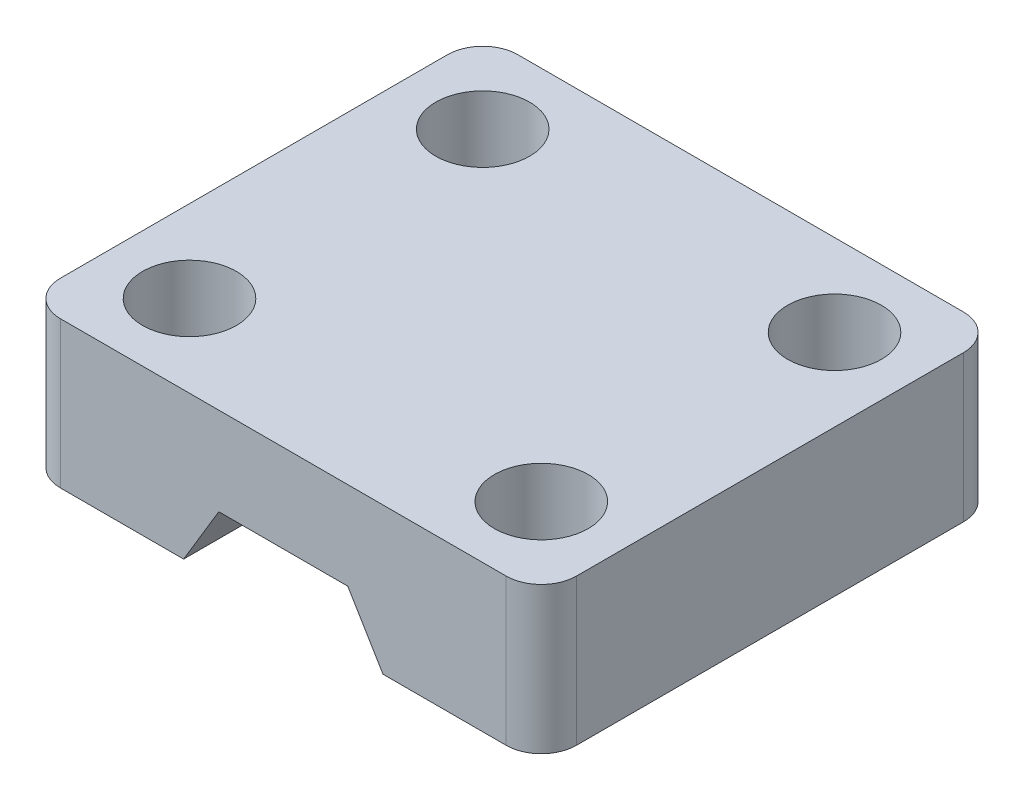
SolidWorks part; units mm, degrees
ref_plane "Front Plane" through (0, 0, 0) normal (0, 0, 1) x (1, 0, 0)
ref_plane "Top Plane" through (0, 0, 0) normal (0, 1, 0) x (1, 0, 0)
ref_plane "Right Plane" through (0, 0, 0) normal (1, 0, 0) x (0, 0, -1)
sketch "Sketch1" plane through (0, 0, 0) normal (0, 0, 1) x (1, 0, 0)
  line L0 (13.5, -12.5) -> (16.5, -7.5)
  line L1 (0, 0) -> (44, 0)
  line L2 (0, 0) -> (0, -12.5)
  line L3 (0, -12.5) -> (13.5, -12.5)
  line L4 (44, 0) -> (44, -12.5)
  line L5 (16.5, -7.5) -> (27.5, -7.5)
  line L6 (27.5, -7.5) -> (30.5, -12.5)
  line L7 (30.5, -12.5) -> (44, -12.5)
  point P9 (22, -7.5)
  point P10 (28.5675, -7.5)
  point P11 (22, 0)
  dimension "D1" = 17
  dimension "D2" = 11
  dimension "D3" = 5
  dimension "D4" = 8.5
  dimension "D5" = 12.5
  dimension "D6" = 44
extrude "Boss-Extrude1" add sketch "Sketch1" along normal blind 39
sketch "Sketch2" plane through (0, 0, 0) normal (0, 1, 0) x (1, 0, 0)
  line L0 (44, 0) -> (0, 0) construction
  line L2 (44, -39) -> (44, 0) construction
  circle A0 centre (7, -7) radius 4
  circle A1 centre (37, -7) radius 4
  circle A2 centre (37, -32) radius 4
  circle A3 centre (7, -32) radius 4
  point P8 (0, 0)
  point P9 (0, 0)
  point P10 (0, 0)
  point P11 (0, 0)
  point P12 (0, 0)
  point P15 (22, 0)
  point P18 (21.0709, -19.6822)
  point P21 (44, -19.5)
  dimension "D3" = 8
  dimension "D1" = 30
  dimension "D2" = 25
  dimension "D4" = 15
  dimension "D5" = 12.5
extrude "Cut-Extrude1" cut sketch "Sketch2" against normal through all
fillet "Fillet1" radius 3 4 edges at (0, -6.25, 0) (44, -6.25, 0) (44, -6.25, 39) (0, -6.25, 39)
